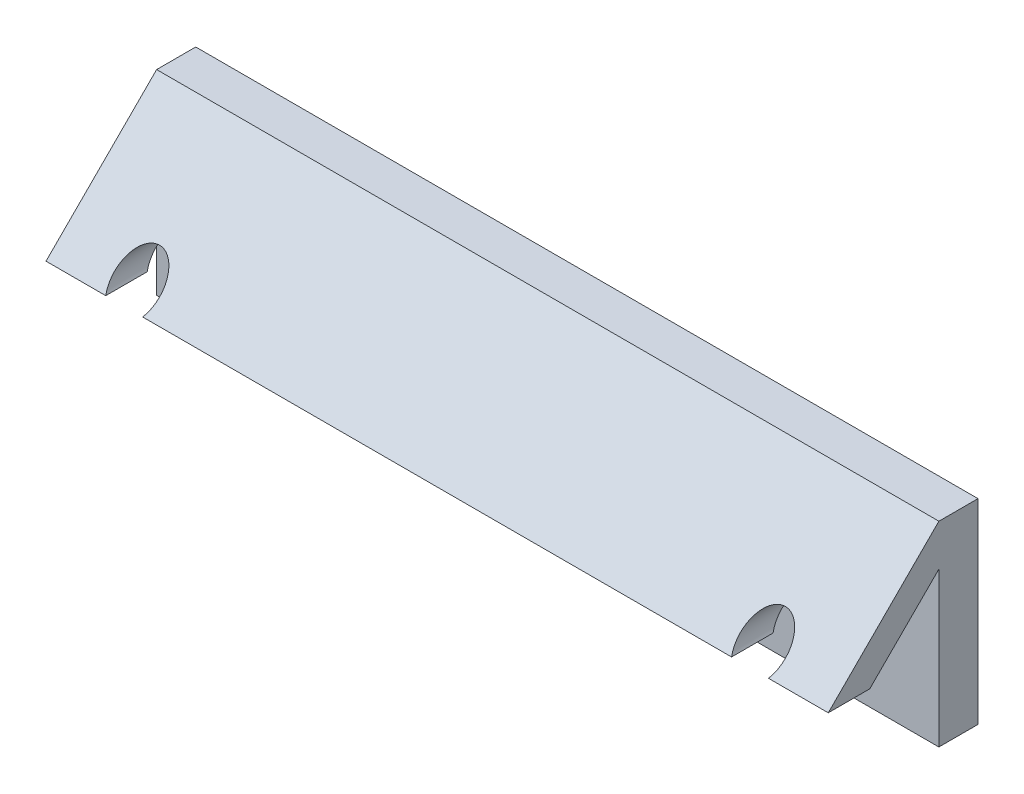
SolidWorks part; units mm, degrees
ref_plane "Front Plane" through (0, 0, 0) normal (0, 0, 1) x (1, 0, 0)
ref_plane "Top Plane" through (0, 0, 0) normal (0, 1, 0) x (1, 0, 0)
ref_plane "Right Plane" through (0, 0, 0) normal (1, 0, 0) x (0, 0, -1)
sketch "Sketch1" plane through (0, 0, 0) normal (0, 0, 1) x (1, 0, 0)
  line L1 (-40, -10) -> (40, -10)
  line L2 (-40, -10) -> (-40, 10)
  line L3 (-40, 10) -> (40, 10)
  line L4 (40, -10) -> (40, 10)
  line L5 (-40, -10) -> (40, 10) construction
  line L6 (-40, 10) -> (40, -10) construction
  point P0 (0, 0)
  dimension "D1" = 20
  dimension "D2" = 80
extrude "Boss-Extrude1" add sketch "Sketch1" along normal blind 4
sketch "Sketch3" plane through (40, 0, 0) normal (1, 0, 0) x (0, 0, -1)
  line L0 (-4, 10) -> (-15.3137, -1.3137)
  line L4 (-15.3137, -1.3137) -> (-11.0711, -1.3137)
  line L5 (-11.0711, -1.3137) -> (-4, 5.7574)
  line L6 (-4, -10) -> (-4, 10) construction
  line L7 (-4, 5.7574) -> (-4, 10)
  point P3 (-15.2571, -1.3489)
  dimension "D1" = 3
  dimension "D2" = 45
  dimension "D3" = 16
extrude "Boss-Extrude2" add sketch "Sketch3" against normal up to surface (80 mm away) up to face at (-40, 0, 2)
sketch "Sketch2" plane through (0, 0, 4) normal (0, 0, 1) x (1, 0, 0)
  line L0 (-40, 5.7574) -> (-40, -10) construction
  line L1 (40, -10) -> (40, 5.7574) construction
  circle A0 centre (-32, 0) radius 2.3
  circle A1 centre (32, 0) radius 2.3
  dimension "D3" = 4.6
  dimension "D1" = 8
  dimension "D2" = 8
extrude "Cut-Extrude1" cut sketch "Sketch2" against normal through all both and the other way through all
